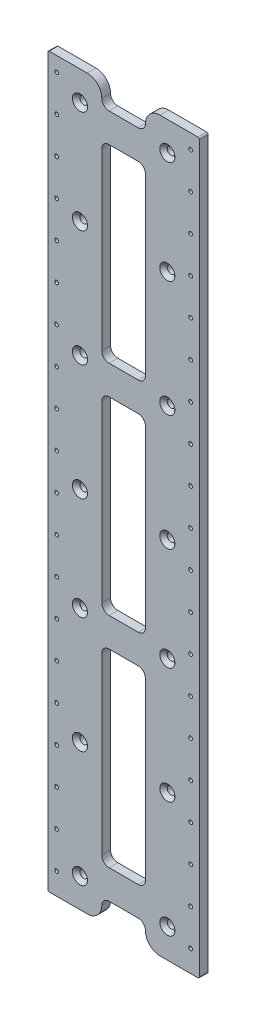
SolidWorks part; units mm, degrees
material "5052-H34"
ref_plane "Front" through (0, 0, 0) normal (0, 0, 1) x (1, 0, 0)
ref_plane "Top" through (0, 0, 0) normal (0, 1, 0) x (1, 0, 0)
ref_plane "Right" through (0, 0, 0) normal (1, 0, 0) x (0, 0, -1)
sketch "Sketch1" plane through (0, 0, 0) normal (0, 0, 1) x (1, 0, 0)
  line L0 (-15, 0) -> (-15, -10)
  line L1 (-10, -15) -> (10, -15)
  line L2 (52, 0) -> (-52, 0)
  line L3 (52, 0) -> (52, -500)
  line L4 (52, -500) -> (-52, -500)
  line L5 (-52, 0) -> (-52, -500)
  line L6 (15, -10) -> (15, 0)
  line L7 (0, 0) -> (0, -35) construction
  line L8 (-30, -500) -> (-30, 0) construction
  line L9 (-15, -500) -> (15, -500)
  line L10 (30, -500) -> (30, 0) construction
  line L11 (-15, -500) -> (-15, -490)
  line L12 (-10, -485) -> (10, -485)
  line L13 (15, -500) -> (15, -490)
  line L16 (-10, -35) -> (10, -35)
  line L17 (-15, -40) -> (-15, -160)
  line L18 (-10, -165) -> (10, -165)
  line L19 (15, -40) -> (15, -160)
  line L20 (-10, -185) -> (10, -185)
  line L21 (-15, -190) -> (-15, -310)
  line L22 (-10, -315) -> (10, -315)
  line L23 (15, -190) -> (15, -310)
  line L24 (-10, -335) -> (10, -335)
  line L25 (-15, -340) -> (-15, -460)
  line L26 (-10, -465) -> (10, -465)
  line L27 (15, -340) -> (15, -460)
  line L28 (-15, -250) -> (-52, -250) construction
  arc A2 (-15, -160) -> (-10, -165) centre (-10, -160) ccw
  arc A6 (10, -165) -> (15, -160) centre (10, -160) ccw
  arc A7 (10, -35) -> (15, -40) centre (10, -40) cw
  arc A8 (-10, -35) -> (-15, -40) centre (-10, -40) ccw
  arc A9 (-10, -335) -> (-15, -340) centre (-10, -340) ccw
  arc A10 (10, -315) -> (15, -310) centre (10, -310) ccw
  arc A11 (-15, -310) -> (-10, -315) centre (-10, -310) ccw
  arc A12 (10, -185) -> (15, -190) centre (10, -190) cw
  arc A13 (-10, -185) -> (-15, -190) centre (-10, -190) ccw
  arc A14 (-15, -460) -> (-10, -465) centre (-10, -460) ccw
  arc A15 (15, -460) -> (10, -465) centre (10, -460) cw
  arc A16 (10, -335) -> (15, -340) centre (10, -340) cw
  arc A17 (-15, -10) -> (-10, -15) centre (-10, -10) ccw
  arc A18 (10, -15) -> (15, -10) centre (10, -10) ccw
  arc A19 (10, -485) -> (15, -490) centre (10, -490) cw
  arc A20 (-15, -490) -> (-10, -485) centre (-10, -490) cw
  point P39 (15, -35)
  point P42 (-15, -35)
  point P63 (15, -15)
  point P66 (15, -485)
  point P69 (-15, -485)
  dimension "D14" = 5
  dimension "D15" = 5
  dimension "D16" = 5
  dimension "D17" = 5
  dimension "D1" = 104
  dimension "D2" = 60
  dimension "D3" = 30
  dimension "D4" = 500
  dimension "D5" = 30
  dimension "D6" = 15
  dimension "D7" = 15
  dimension "D8" = 15
  dimension "D9" = 30
  dimension "D10" = 130
  dimension "D11" = 20
  dimension "D12" = 20
  dimension "D13" = 30
extrude "Boss-Extrude1" add sketch "Sketch1" along normal blind 6 contours L13 L4 L3 L2 L6 L1 L0 L5 L11 L12 L16 L19 L18 L17 L20 L23 L22 L21 L24 L27 L26 L25 region at (-20.107, -5, 0)
hole_wizard "CSK for M5 Countersunk Flat Head Screw1" positions "Sketch2" profile "Sketch3" countersink size "M5" standard "ISO" end condition through all
sketch "Sketch2" plane through (0, 0, 6) normal (0, 0, 1) x (1, 0, 0)
  line L0 (30, -500) -> (30, 0) construction
  line L1 (-30, -500) -> (-30, 0) construction
  line L2 (30, -500) -> (30, 0) construction
  line L3 (-30, -500) -> (-30, 0) construction
  line L5 (52, 0) -> (-52, 0) construction
  line L6 (52, -500) -> (-52, -500) construction
  point P5 (-30, -20)
  point P7 (30, -20)
  point P9 (-30, -90.6667)
  point P11 (30, -90.6667)
  point P13 (-30, -170.3333)
  point P15 (30, -170.3333)
  point P17 (30, -250)
  point P19 (-30, -250)
  point P21 (-30, -320.6667)
  point P23 (30, -320.6667)
  point P25 (-30, -400.3333)
  point P27 (30, -400.3333)
  point P29 (-30, -480)
  point P31 (30, -480)
  point P36 (-30, -184.8683)
  dimension "D1" = 20
  dimension "D2" = 20
  dimension "D3" = 79.6667
  dimension "D4" = 79.6667
  dimension "D5" = 79.6667
  dimension "D6" = 79.6667
sketch "Sketch3" plane through (30, -480, 6) normal (1, 0, 0) x (0, -1, 0)
  line L0 (0, 0) -> (0, 6)
  line L1 (0, 6) -> (2.65, 6)
  line L2 (2.65, 6) -> (2.65, 2.55)
  line L3 (2.65, 2.55) -> (5.2, 0)
  line L5 (5.2, 0) -> (0, 0)
  line L6 (-2.65, 2.55) -> (-5.2, 0) construction
  line L11 (0, -6.35) -> (0, 107.95) construction
  dimension "Thru Hole Dia." = 5.3
  dimension "Thru Hole Depth" = 6
  dimension "Near C'Sink Dia." = 10.4
  dimension "Near C'Sink Angle" = 90
hole_wizard "Ø2.6 (2.6) Diameter Hole1" positions "Sketch4" profile "Sketch5" hole size "Ø2.6" standard "ISO" end condition through all
sketch "Sketch4" plane through (0, 0, 6) normal (0, 0, 1) x (1, 0, 0)
  line L1 (-46, 0) -> (-46, -500) construction
  line L2 (52, 0) -> (-52, 0) construction
  line L3 (52, -500) -> (-52, -500) construction
  line L5 (0, 0) -> (0, 41.2983) construction
  point P18 (-46, -10)
  point P28 (46, -10)
  point P29 (46, -35)
  point P30 (46, -60)
  point P31 (46, -85)
  point P32 (46, -110)
  point P33 (46, -135)
  point P34 (46, -160)
  point P35 (46, -185)
  point P36 (46, -210)
  point P37 (46, -235)
  point P38 (46, -260)
  point P39 (46, -285)
  point P40 (46, -310)
  point P41 (46, -335)
  point P42 (46, -360)
  point P43 (46, -385)
  point P44 (46, -410)
  point P45 (46, -435)
  point P46 (46, -460)
  point P47 (46, -485)
  point P48 (46, -510)
  point P49 (-46, -35)
  point P50 (-46, -60)
  point P51 (-46, -85)
  point P52 (-46, -110)
  point P53 (-46, -135)
  point P54 (-46, -160)
  point P55 (-46, -185)
  point P56 (-46, -210)
  point P57 (-46, -235)
  point P58 (-46, -260)
  point P59 (-46, -285)
  point P60 (-46, -310)
  point P61 (-46, -335)
  point P62 (-46, -360)
  point P63 (-46, -385)
  point P64 (-46, -410)
  point P65 (-46, -435)
  point P66 (-46, -460)
  point P67 (-46, -485)
  point P68 (-46, -510)
  dimension "D1" = 46
  dimension "D2" = 10
  dimension "D3" = 2
  dimension "D4" = 21
sketch "Sketch5" plane through (-46, -510, 6) normal (1, 0, 0) x (0, -1, 0)
  line L0 (0, 0) -> (0, 6)
  line L1 (0, 6) -> (1.3, 6)
  line L2 (1.3, 6) -> (1.3, 0)
  line L5 (1.3, 0) -> (0, 0)
  line L11 (0, -6.35) -> (0, 107.95) construction
  dimension "Thru Hole Dia." = 2.6
  dimension "Thru Hole Depth" = 6
fillet "Fillet1" radius 10 4 edges at (15, 0, 3) (-15, 0, 3) (15, -500, 3) (-15, -500, 3)
fillet "Fillet2" radius 1 4 edges at (52, -500, 3) (-52, -500, 3) (52, 0, 3) (-52, 0, 3)
